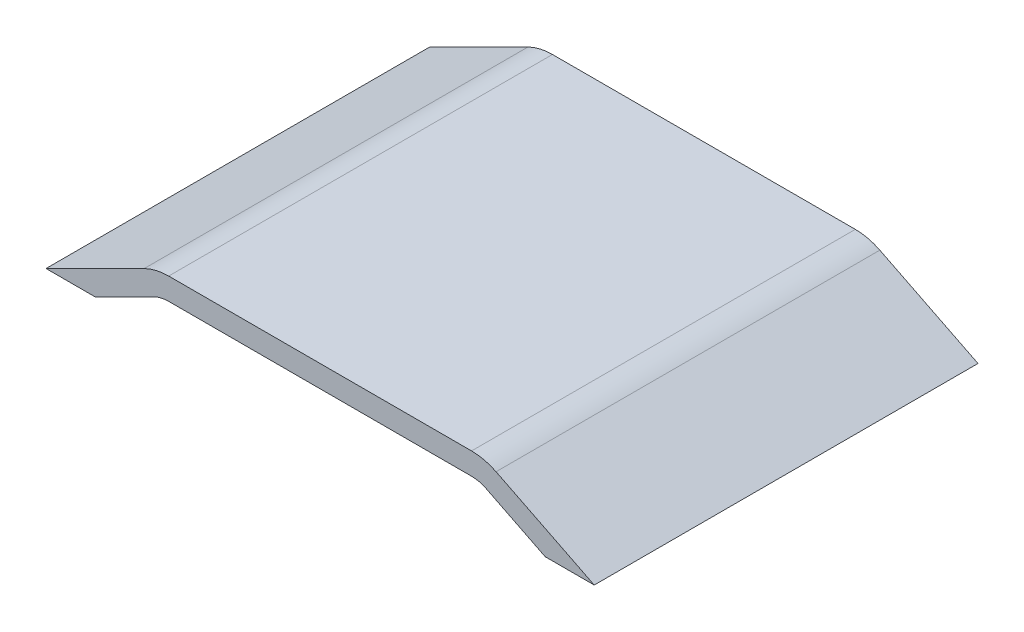
SolidWorks part; units mm, degrees
ref_plane "Front Plane" through (0, 0, 0) normal (0, 0, 1) x (1, 0, 0)
ref_plane "Top Plane" through (0, 0, 0) normal (0, 1, 0) x (1, 0, 0)
ref_plane "Right Plane" through (0, 0, 0) normal (1, 0, 0) x (0, 0, -1)
sketch "Sketch1" plane through (0, 0, 0) normal (0, 0, 1) x (1, 0, 0)
  line L0 (-63.5, -6.35) -> (-38.0767, 6.35)
  line L1 (63.5, -6.35) -> (-63.5, -6.35) construction
  line L2 (63.5, -6.35) -> (63.5, 6.35) construction
  line L3 (63.5, 6.35) -> (-63.5, 6.35) construction
  line L4 (-63.5, -6.35) -> (-63.5, 6.35) construction
  line L5 (63.5, -6.35) -> (-63.5, 6.35) construction
  line L6 (63.5, 6.35) -> (-63.5, -6.35) construction
  line L7 (-38.0767, 6.35) -> (38.0767, 6.35)
  line L8 (38.0767, 6.35) -> (63.5, -6.35)
  line L9 (63.5, -6.35) -> (-63.5, -6.35)
  point P0 (0, 0)
  dimension "D1" = 127
  dimension "D2" = 12.7
extrude "Boss-Extrude1" add sketch "Sketch1" along normal blind 88.9
fillet "Fillet1" radius 12.7 2 edges at (-38.0767, 6.35, 44.45) (38.0767, 6.35, 44.45)
sketch "Sketch3" plane through (0, 0, 88.9) normal (0, 0, 1) x (1, 0, 0)
  line L27 (-61.2298, -10.8945) -> (61.2298, -10.8945)
  line L30 (61.2298, -10.8945) -> (38.4864, 0.4668)
  line L31 (35.0811, 1.27) -> (-35.0811, 1.27)
  line L32 (-38.4864, 0.4668) -> (-61.2298, -10.8945)
  line L33 (61.2298, -10.8945) -> (38.4864, 0.4668)
  line L34 (35.0811, 1.27) -> (-35.0811, 1.27)
  line L35 (-38.4864, 0.4668) -> (-61.2298, -10.8945)
  arc A17 (38.4864, 0.4668) -> (35.0811, 1.27) centre (35.0811, -6.35) ccw
  arc A18 (-35.0811, 1.27) -> (-38.4864, 0.4668) centre (-35.0811, -6.35) ccw
  arc A19 (38.4864, 0.4668) -> (35.0811, 1.27) centre (35.0811, -6.35) ccw
  arc A20 (-35.0811, 1.27) -> (-38.4864, 0.4668) centre (-35.0811, -6.35) ccw
  dimension "D1" = 5.08
extrude "Cut-Extrude1" cut sketch "Sketch3" against normal up to next
ref_plane "Plane1" through (0, 0, 44.45) normal (0, 0, -1) x (-1, 0, 0)
sketch "Sketch4" plane through (0, 0, 0) normal (0, 1, 0) x (1, 0, 0)
  circle A0 centre (-52.8588, -9.8061) radius 3.0953
